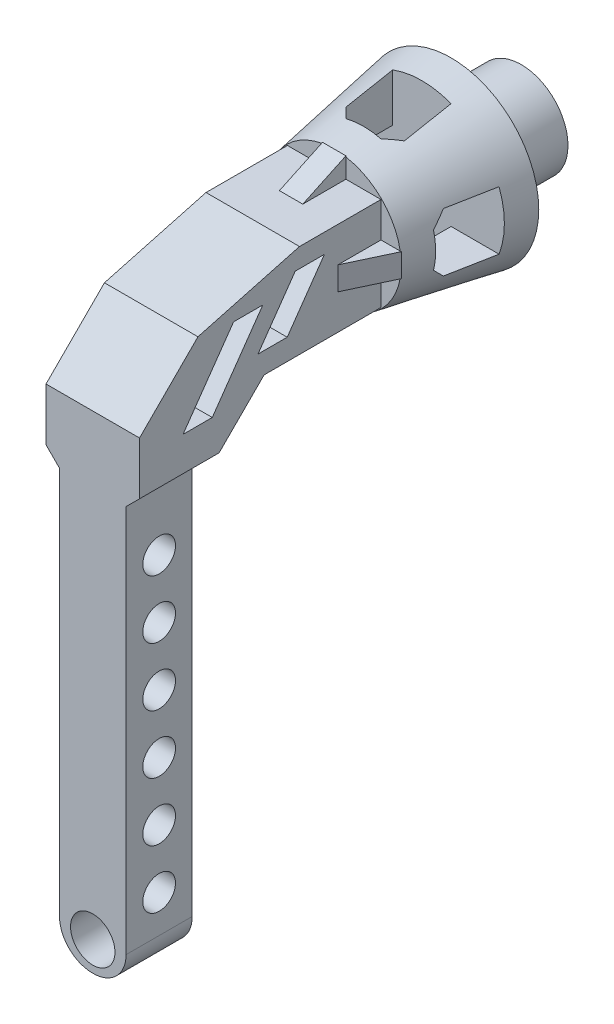
SolidWorks part; units mm, degrees
ref_plane "前视基准面" through (0, 0, 0) normal (0, 0, 1) x (1, 0, 0)
ref_plane "上视基准面" through (0, 0, 0) normal (0, 1, 0) x (1, 0, 0)
ref_plane "右视基准面" through (0, 0, 0) normal (1, 0, 0) x (0, 0, -1)
other "Configuration Table"
sketch "草图1" plane through (0, 0, 0) normal (0, 0, 1) x (1, 0, 0)
  circle A0 centre (0, 0) radius 2.5
  circle A1 centre (0, 0) radius 4
  dimension "D1" = 5
  dimension "D2" = 8
extrude "凸台-拉伸1" add sketch "草图1" along normal blind 6
sketch "草图2" plane through (0, 0, 6) normal (0, 0, 1) x (1, 0, 0)
  circle A0 centre (0, 0) radius 7.5
  dimension "D1" = 15
extrude "凸台-拉伸2" add sketch "草图2" along normal blind 10 draft 10 contours A0
chamfer "倒角1" distance 1 angle 45 1 edges at (2.5, 0, 0)
sketch "草图5" plane through (0, 0, 6) normal (0, 0, -1) x (-1, 0, 0)
  circle A0 centre (0, 0) radius 2.5 construction
  circle A1 centre (0, 0) radius 2.5
curve "螺旋线/涡状线2" pitch 0.8 height 5.6 turns 7
ref_plane "基准面1" through (1.7678, 1.7678, 0.4) normal (-0.7062, 0.7062, -0.0509) x (0.6934, 0.7044, 0.1517)
sketch "草图6" plane through (1.7678, 1.7678, 0.4) normal (-0.7062, 0.7062, -0.0509) x (0.6934, 0.7044, 0.1517)
  line L0 (0.3452, 0.0295) -> (0, 0) construction
  line L1 (-0.017, 0.1993) -> (0.017, -0.1993)
  line L2 (0.017, -0.1993) -> (0.3452, 0.0295)
  line L3 (0.3452, 0.0295) -> (-0.017, 0.1993)
  circle A0 centre (0.1151, 0.0098) radius 0.1155 construction
  dimension "D1" = 0.4
sweep "切除-扫描1" cut profiles "草图6" path "螺旋线/涡状线2"
sketch "草图7" plane through (0, 0, 16) normal (0, 0, 1) x (1, 0, 0)
  line L0 (-1000, 0) -> (-4, 0) construction
  line L3 (4, -4) -> (-4, -4)
  line L4 (-4, 4) -> (-4, -4)
  line L5 (0, 1002.4932) -> (0, 4) construction
  line L6 (4, 4) -> (-4, 4)
  line L7 (4, 4) -> (4, -4)
  line L8 (4, 0) -> (1005.5512, 0) construction
  line L9 (0, -4) -> (0, -1003.4308) construction
  dimension "D1" = 8
extrude "凸台-拉伸5" add sketch "草图7" along normal blind 10
sketch "草图12" plane through (-4, 0, 0) normal (-1, 0, 0) x (0, 0, 1)
  line L0 (26, 4) -> (26, -4)
  line L1 (26, -4) -> (34, 4)
  line L2 (34, 4) -> (26, 4)
  dimension "D1" = 8
extrude "凸台-拉伸6" add sketch "草图12" against normal up to surface (8 mm away) up to face at (4, 0, 21)
sketch "草图13" plane through (0, -15, 15) normal (0, -0.7071, 0.7071) x (1, 0, 0)
  line L0 (4, 26.8701) -> (4, 15.5563) construction
  line L1 (-4, 15.5563) -> (4, 15.5563)
  line L2 (-4, 15.5563) -> (-4, 23.5563)
  line L3 (-4, 23.5563) -> (4, 23.5563)
  line L4 (4, 15.5563) -> (4, 23.5563)
  dimension "D1" = 8
extrude "凸台-拉伸7" add sketch "草图13" along normal blind 7.07
sketch "草图15" plane through (-4, 0, 0) normal (-1, 0, 0) x (0, 0, 1)
  line L0 (36.6561, -3.3424) -> (36.6561, -8.9992)
  line L1 (36.6561, -8.9992) -> (30.9992, -8.9992)
  line L2 (36.6561, -3.3424) -> (30.9992, -8.9992) construction
  line L3 (36.6561, -3.3424) -> (30.9992, -8.9992)
  dimension "D1" = 45
extrude "凸台-拉伸8" add sketch "草图15" against normal up to surface (8 mm away) contours L1 L3 L0 up to face at (4, -1.5264, 27.3303)
sketch "草图16" plane through (0, -8.9992, 0) normal (0, -1, 0) x (1, 0, 0)
  line L0 (-4, 30.9992) -> (4, 30.9992) construction
  line L1 (-2.85, 30.9992) -> (2.85, 30.9992)
  line L2 (-2.85, 30.9992) -> (-2.85, 36.6561)
  line L3 (-2.85, 36.6561) -> (2.85, 36.6561)
  line L4 (2.85, 30.9992) -> (2.85, 36.6561)
  line L5 (4, 36.6561) -> (-4, 36.6561) construction
  line L6 (4, 30.9992) -> (4, 36.6561) construction
  line L7 (-4, 36.6561) -> (-4, 30.9992) construction
  dimension "D1" = 1.15
  dimension "D2" = 1.15
extrude "凸台-拉伸9" add sketch "草图16" along normal blind 31
sketch "草图17" plane through (0, 0, 30.9992) normal (0, 0, -1) x (-1, 0, 0)
  line L0 (0, -39.9992) -> (0, -44.9992) construction
  line L1 (-2.85, -39.9992) -> (2.85, -39.9992)
  line L2 (-2.85, -39.9992) -> (-2.85, -44.9992)
  line L3 (-2.85, -44.9992) -> (2.85, -44.9992)
  line L4 (2.85, -39.9992) -> (2.85, -44.9992)
  line L5 (-2.85, -42.4992) -> (2.85, -42.4992) construction
  circle A0 centre (0, -42.4992) radius 1.9
  dimension "D3" = 3.8
  dimension "D1" = 5.7
  dimension "D2" = 5
extrude "凸台-拉伸10" add sketch "草图17" against normal up to surface (5.6569 mm away) up to face at (0, -15.335, 36.6561)
fillet "圆角1" radius 2.8 2 edges at (-2.85, -44.9992, 33.8277) (2.85, -44.9992, 33.8277)
sketch "草图18" plane through (4, 0, 0) normal (1, 0, 0) x (0, 0, -1)
  line L0 (-31.6569, 1.6569) -> (-22.9688, 4)
  line L1 (-34, 4) -> (-16, 4) construction
  line L2 (-22.9688, 4) -> (-34, 4)
  line L3 (-34, 4) -> (-31.6569, 1.6569)
extrude "切除-拉伸2" cut sketch "草图18" against normal through all
chamfer "倒角2" distance 1.15 angle 45 2 edges at (4, -8.9992, 33.8277) (-4, -8.9992, 33.8277)
sketch "草图19" plane through (0, 0, 0) normal (0, 1, 0) x (1, 0, 0)
  line L0 (-5.7367, -16) -> (-4, -19.6902)
  line L1 (-4, -22.9688) -> (-4, -16) construction
  line L2 (-4, -19.6902) -> (-4, -16)
  line L3 (-4, -16) -> (-5.7367, -16)
  line L4 (4, -16) -> (4, -19.6902)
  line L5 (4, -22.9688) -> (4, -16) construction
  line L6 (4, -19.6902) -> (5.7367, -16)
  line L7 (5.7367, -16) -> (4, -16)
extrude "凸台-拉伸11" add sketch "草图19" along normal blind 1 and the other way blind 1
sketch "草图20" plane through (0, 0, 0) normal (1, 0, 0) x (0, 0, -1)
  line L0 (-19.6902, -4) -> (-16, -5.7367)
  line L1 (-26, -4) -> (-16, -4) construction
  line L2 (-16, -1) -> (-16, -5.7367) construction
  line L3 (-16, -5.7367) -> (-16, -4)
  line L4 (-16, -4) -> (-19.6902, -4)
  line L5 (-19.6902, 4) -> (-16, 5.7367)
  line L6 (-22.9688, 4) -> (-16, 4) construction
  line L7 (-16, 5.7367) -> (-16, 1) construction
  line L8 (-16, 5.7367) -> (-16, 4)
  line L9 (-16, 4) -> (-19.6902, 4)
extrude "凸台-拉伸12" add sketch "草图20" along normal blind 1 and the other way blind 1
sketch "草图21" plane through (0, 0, 0) normal (0, 1, 0) x (1, 0, 0)
  line L0 (0, -6) -> (0, -8.5) construction
  line L1 (7.5, -6) -> (-7.5, -6) construction
  line L2 (-6.6184, -11) -> (-2.5, -11) construction
  line L3 (-7.5, -6) -> (-5.7367, -16) construction
  line L4 (5.7367, -16) -> (7.5, -6) construction
  line L5 (2.5, -13.5) -> (2.5, -8.5)
  line L8 (2.5, -8.5) -> (-2.5, -8.5)
  line L9 (-2.5, -13.5) -> (-2.5, -8.5)
  line L10 (2.5, -13.5) -> (-2.5, -13.5)
  line L11 (0, -13.5) -> (0, -16) construction
  line L12 (2.5, -11) -> (6.6184, -11) construction
extrude "切除-拉伸3" cut sketch "草图21" against normal blind 10 and the other way blind 10
sketch "草图22" plane through (0, 0, 0) normal (1, 0, 0) x (0, 0, -1)
  line L0 (-6, 0) -> (-8.5, 0) construction
  line L1 (-6, -7.5) -> (-6, 7.5) construction
  line L2 (8.25, 0) -> (-8.25, 0) construction
  line L3 (-16, -1) -> (-16, 0) construction
  line L4 (-13.5, -2.5) -> (-8.5, -2.5)
  line L6 (-13.5, -2.5) -> (-13.5, 2.5)
  line L7 (-13.5, 2.5) -> (-8.5, 2.5)
  line L8 (-8.5, -2.5) -> (-8.5, 2.5)
  line L9 (-13.5, 0) -> (-16, 0) construction
  dimension "D1" = 2.5
extrude "切除-拉伸4" cut sketch "草图22" against normal blind 10 and the other way blind 10
chamfer "倒角4" distance 1 angle 45 8 edges at (2.5, -4.0745, 13.5) (4.0745, -2.5, 13.5) (4.0745, 2.5, 13.5) (2.5, 4.0745, 13.5) (-2.5, 4.0745, 13.5) (-4.0745, 2.5, 13.5) (-2.5, -4.0745, 13.5) (-4.0745, -2.5, 13.5)
sketch "草图23" plane through (0, 0, 6) normal (0, 0, -1) x (-1, 0, 0)
  circle A0 centre (0, 0) radius 2.5
  dimension "D1" = 5
extrude "切除-拉伸5" cut sketch "草图23" against normal blind 2
chamfer "倒角5" distance 2 angle 45 1 edges at (-2.5, 0, 8)
sketch "草图24" plane through (-4, 0, 0) normal (-1, 0, 0) x (0, 0, 1)
  line L0 (20.8357, 2.355) -> (23.3357, 2.355)
  line L1 (23.3357, 2.355) -> (26.5205, -2.1934)
  line L2 (26.5205, -2.1934) -> (24.0205, -2.1934)
  line L3 (24.0205, -2.1934) -> (20.8357, 2.355)
  line L4 (26.1093, 1.2383) -> (28.6093, 1.2383)
  line L5 (28.6093, 1.2383) -> (32.9324, -4.9358)
  line L6 (32.9324, -4.9358) -> (30.4324, -4.9358)
  line L7 (30.4324, -4.9358) -> (26.1093, 1.2383)
  point P8 (0, 0)
  dimension "D1" = 2.5
  dimension "D2" = 125
  dimension "D3" = 2.5
extrude "切除-拉伸8" cut sketch "草图24" against normal blind 10
sketch "草图26" plane through (2.85, 0, 0) normal (1, 0, 0) x (0, 0, -1)
  line L0 (-33.8277, -8.9992) -> (-33.8277, -44.9992) construction
  line L1 (-30.9992, -8.9992) -> (-36.6561, -8.9992) construction
  line L2 (-30.9992, -44.9992) -> (-36.6561, -44.9992) construction
  line L3 (-33.8277, -13.9992) -> (-33.8277, -18.9992) construction
  circle A0 centre (-33.8277, -13.9992) radius 1.4
  circle A1 centre (-33.8277, -18.9992) radius 1.4
  circle A2 centre (-33.8277, -23.9992) radius 1.4
  circle A3 centre (-33.8277, -28.9992) radius 1.4
  circle A4 centre (-33.8277, -33.9992) radius 1.4
  circle A5 centre (-33.8277, -38.9992) radius 1.4
  dimension "D1" = 2.8
  dimension "D2" = 5
  dimension "D4" = 5
  dimension "D3" = 6
extrude "切除-拉伸9" cut sketch "草图26" against normal blind 10
